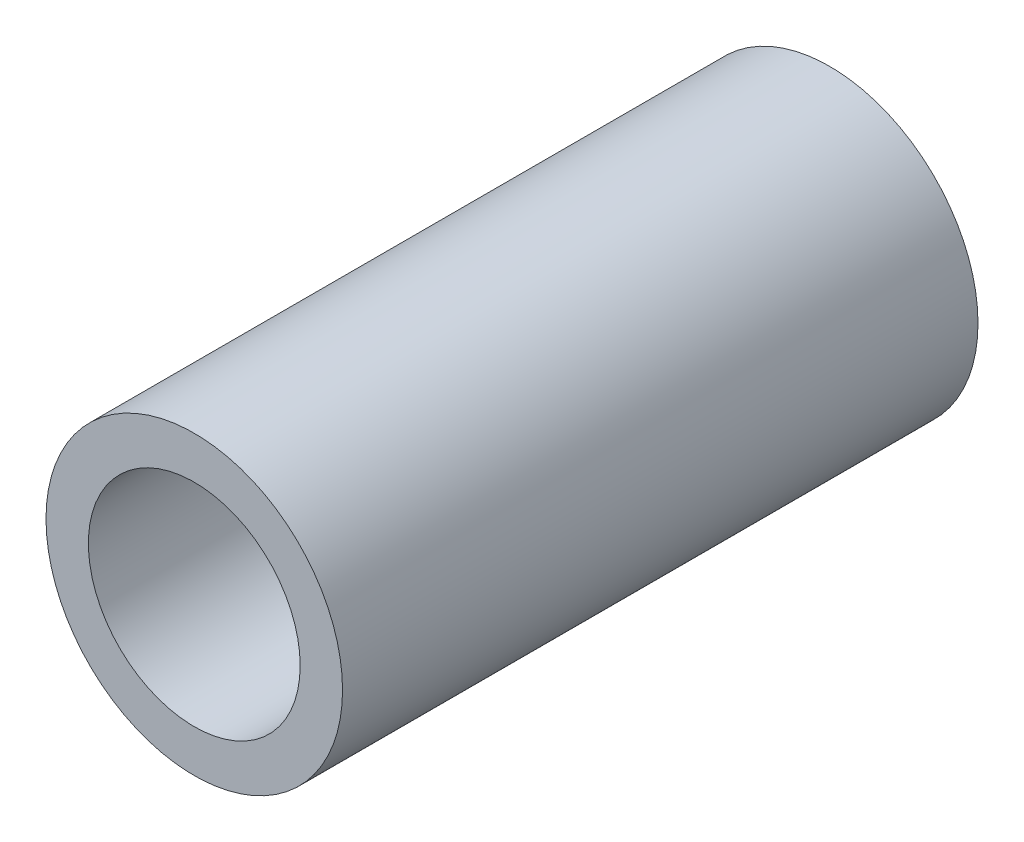
SolidWorks part; units mm, degrees
ref_plane "Спереди" through (0, 0, 0) normal (0, 0, 1) x (1, 0, 0)
ref_plane "Сверху" through (0, 0, 0) normal (0, 1, 0) x (1, 0, 0)
ref_plane "Справа" through (0, 0, 0) normal (1, 0, 0) x (0, 0, -1)
sketch "Эскиз1" plane through (0, 0, 0) normal (0, 0, 1) x (1, 0, 0)
  circle A0 centre (0, 0) radius 5
  dimension "D1" = 10
extrude "Вытянуть-Тонкостенный1" add sketch "Эскиз1" along normal blind 30 thin contours A0 thin type one direction wall 2
